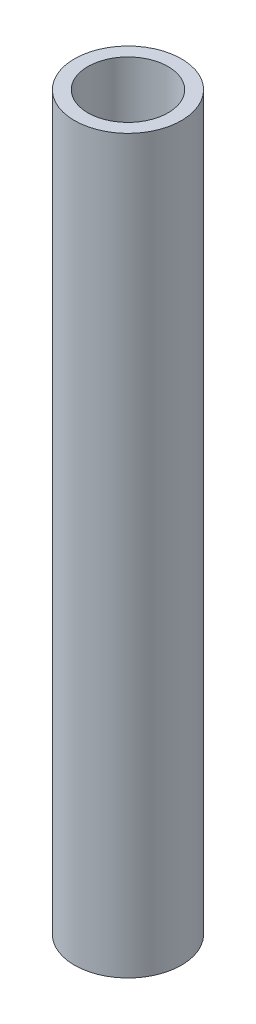
SolidWorks part; units mm, degrees
material "6061 Alloy"
ref_plane "Front Plane" through (0, 0, 0) normal (0, 0, 1) x (1, 0, 0)
ref_plane "Top Plane" through (0, 0, 0) normal (0, 1, 0) x (1, 0, 0)
ref_plane "Right Plane" through (0, 0, 0) normal (1, 0, 0) x (0, 0, -1)
sketch "Sketch1" plane through (0, 0, 0) normal (0, 1, 0) x (1, 0, 0)
  circle A0 centre (0, 0) radius 4.7625
  circle A1 centre (0, 0) radius 6.35
  dimension "D1" = 12.7
  dimension "D2" = 9.525
extrude "Boss-Extrude1" add sketch "Sketch1" along normal blind 86.825
